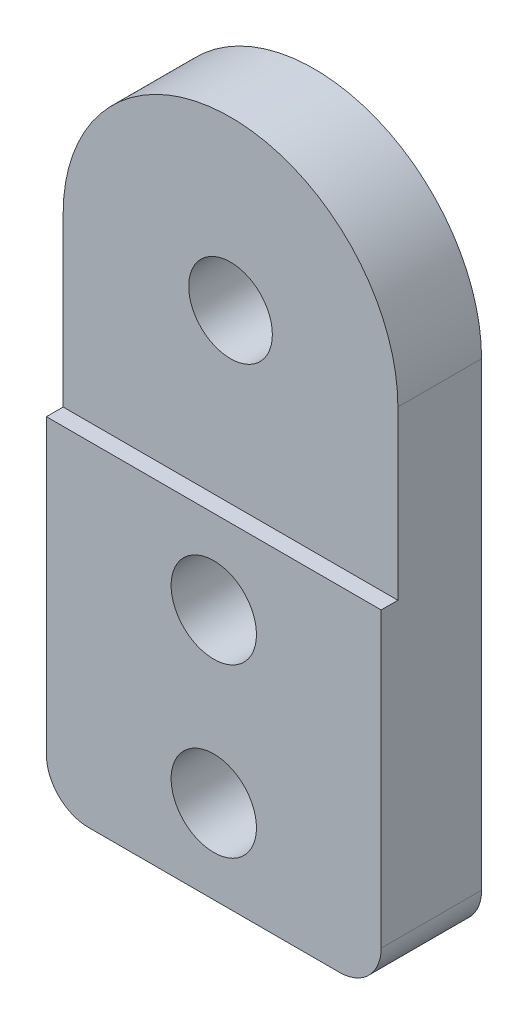
SolidWorks part; units mm, degrees
ref_plane "Front Plane" through (0, 0, 0) normal (0, 0, 1) x (1, 0, 0)
ref_plane "Top Plane" through (0, 0, 0) normal (0, 1, 0) x (1, 0, 0)
ref_plane "Right Plane" through (0, 0, 0) normal (1, 0, 0) x (0, 0, -1)
sketch "Sketch1" plane through (0, 0, 0) normal (0, 0, 1) x (1, 0, 0)
  line L0 (-10, 0) -> (-10, -30)
  line L1 (10, 0) -> (10, -30)
  line L2 (10, -30) -> (-10, -30)
  line L3 (0, -1000) -> (0, 49000) construction
  line L4 (-1002.2178, -10) -> (48997.7822, -10) construction
  arc A0 (10, 0) -> (-10, 0) centre (0, 0) ccw
  circle A1 centre (0, -25) radius 2.55
  circle A2 centre (0, -15) radius 2.55
  dimension "D1" = 20
  dimension "D3" = 5.1
  dimension "D4" = 5.1
  dimension "D5" = 10
  dimension "D6" = 5
  dimension "D2" = 20
  dimension "D7" = 10
extrude "Boss-Extrude1" add sketch "Sketch1" along normal blind 6
sketch "Sketch2" plane through (0, 0, 6) normal (0, 0, 1) x (1, 0, 0)
  circle A0 centre (0, 0) radius 2.5
  dimension "D1" = 5
extrude "Cut-Extrude1" cut sketch "Sketch2" against normal through all
sketch "Sketch3" plane through (0, 0, 6) normal (0, 0, 1) x (1, 0, 0)
  line L0 (-10, -30) -> (10, -30) construction
  line L1 (-20, 10) -> (20, 10)
  line L2 (-20, 10) -> (-20, -10)
  line L3 (-20, -10) -> (20, -10)
  line L4 (20, 10) -> (20, -10)
  line L5 (-20, 10) -> (20, -10) construction
  line L6 (-20, -10) -> (20, 10) construction
  point P0 (0, 0)
  dimension "D1" = 20
  dimension "D2" = 40
extrude "Cut-Extrude2" cut sketch "Sketch3" against normal blind 1
fillet "Fillet1" radius 2.5 2 edges at (10, -30, 3) (-10, -30, 3)
